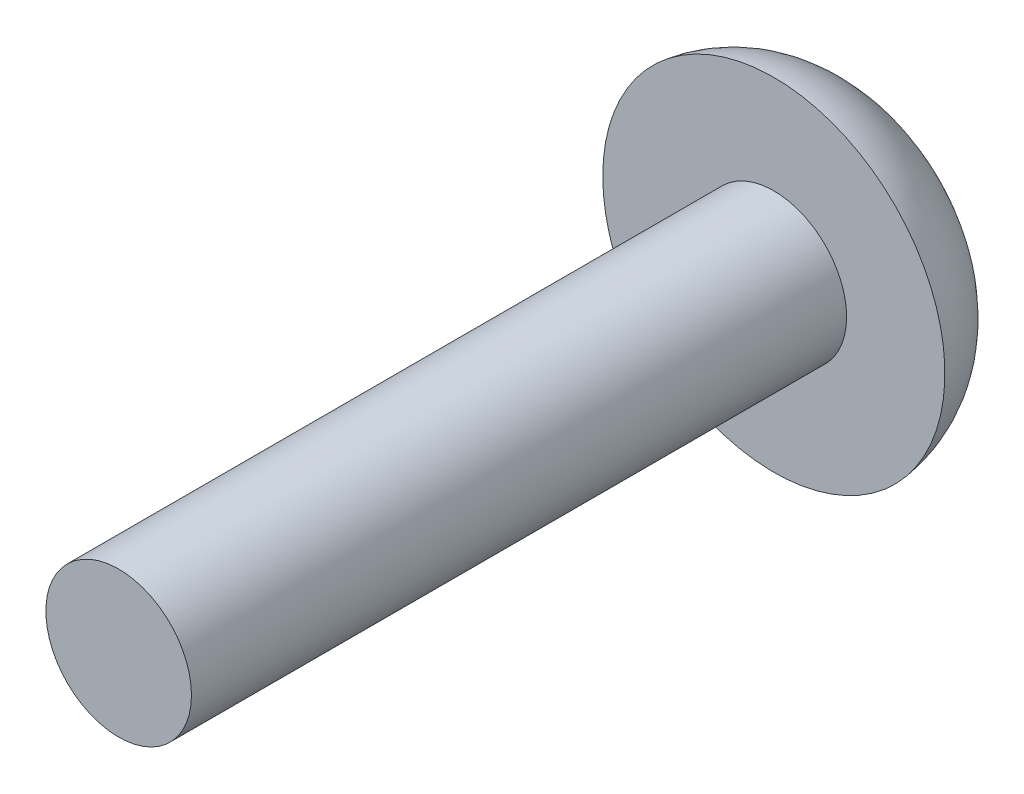
SolidWorks part; units mm, degrees
ref_plane "前视基准面" through (0, 0, 0) normal (0, 0, 1) x (1, 0, 0)
ref_plane "上视基准面" through (0, 0, 0) normal (0, 1, 0) x (1, 0, 0)
ref_plane "右视基准面" through (0, 0, 0) normal (1, 0, 0) x (0, 0, -1)
sketch "草图1" plane through (0, 0, 0) normal (0, 0, 1) x (1, 0, 0)
  circle A0 centre (0, 0) radius 2
extrude "凸台-拉伸1" add sketch "草图1" along normal blind 18
sketch "草图2" plane through (0, 0, 0) normal (0, 0, -1) x (-1, 0, 0)
  circle A0 centre (0, 0) radius 4.7
extrude "凸台-拉伸2" add sketch "草图2" along normal blind 2.65
fillet "圆角2" radius 3 1 edges at (-4.7, 0, -2.65)
